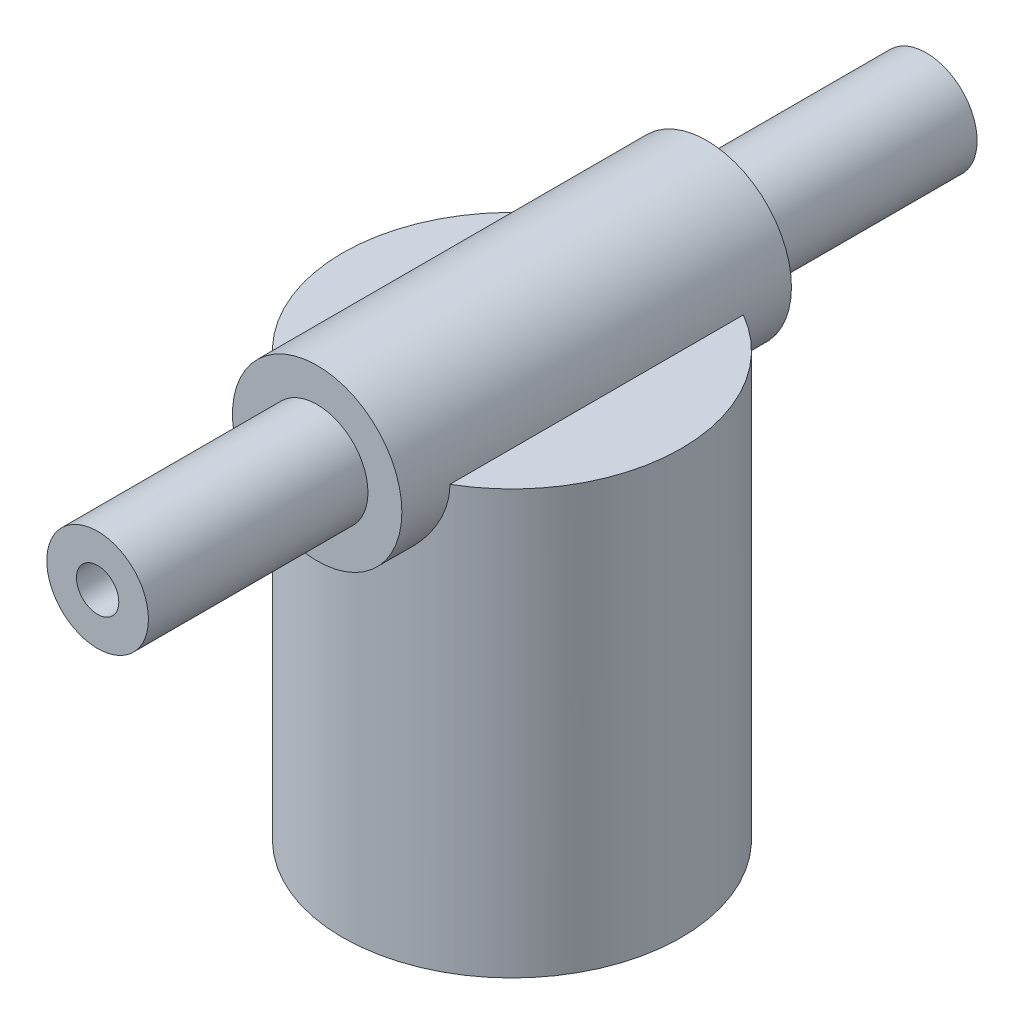
SolidWorks part; units mm, degrees
ref_plane "Front Plane" through (0, 0, 0) normal (0, 0, 1) x (1, 0, 0)
ref_plane "Top Plane" through (0, 0, 0) normal (0, 1, 0) x (1, 0, 0)
ref_plane "Right Plane" through (0, 0, 0) normal (1, 0, 0) x (0, 0, -1)
sketch "Sketch1" plane through (0, 0, 0) normal (0, 1, 0) x (1, 0, 0)
  circle A0 centre (0, 0) radius 20
  dimension "D1" = 40
extrude "Boss-Extrude1" add sketch "Sketch1" along normal blind 50 contours A0
sketch "Sketch2" plane through (0, 0, 0) normal (0, 0, 1) x (1, 0, 0)
  line L0 (20, 50) -> (-20, 50) construction
  circle A0 centre (0, 50) radius 6
  dimension "D1" = 12
extrude "Boss-Extrude2" add sketch "Sketch2" along normal mid plane 97.84
fillet "Fillet1" radius 3 2 edges at (0.891, 44.0665, -19.9801) (-1.4259, 44.1719, 19.9491)
ref_plane "Plane1" through (0, 30, 0) normal (0, 1, 0) x (1, 0, 0)
sketch "Sketch3" plane through (0, 0, 48.92) normal (0, 0, 1) x (1, 0, 0)
  circle A0 centre (0, 50) radius 2.5
  dimension "D1" = 5
extrude "Cut-Extrude1" cut sketch "Sketch3" against normal through all
sketch "Sketch4" plane through (0, 0, 0) normal (0, 0, 1) x (1, 0, 0)
  circle A0 centre (0, 50) radius 10
  dimension "D1" = 20
extrude "Boss-Extrude3" add sketch "Sketch4" along normal mid plane 46
